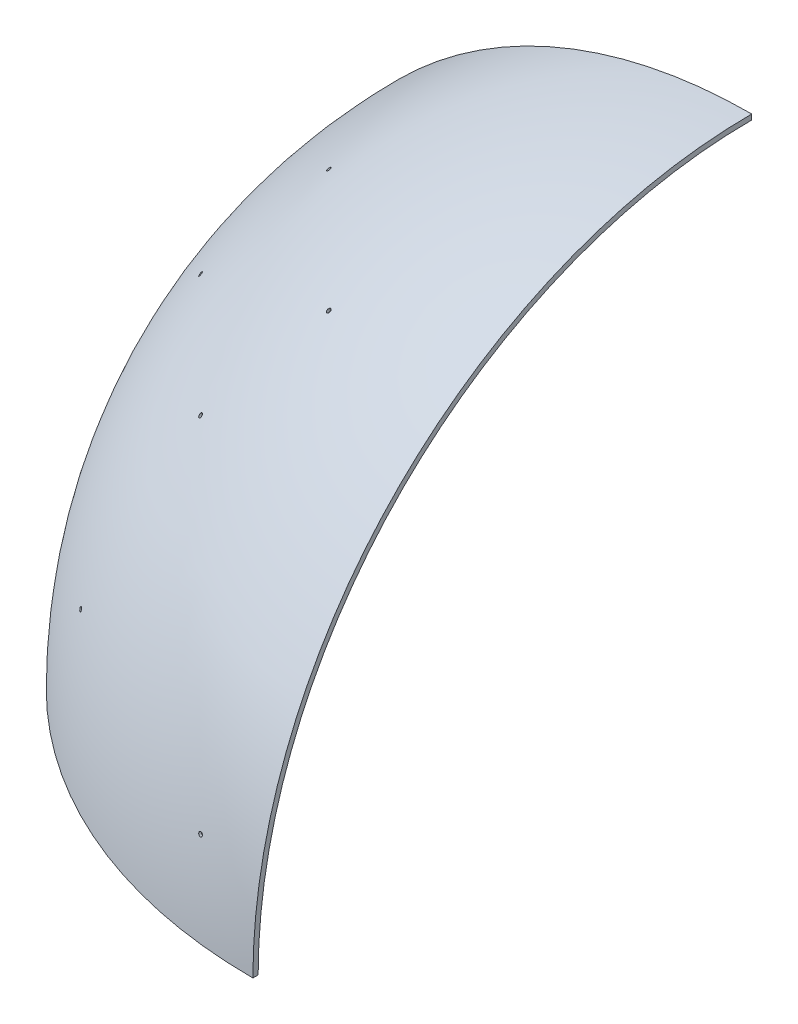
SolidWorks part; units mm, degrees
ref_plane "Front" through (0, 0, 0) normal (0, 0, 1) x (1, 0, 0)
ref_plane "Top" through (0, 0, 0) normal (0, 1, 0) x (1, 0, 0)
ref_plane "Right" through (0, 0, 0) normal (1, 0, 0) x (0, 0, -1)
sketch "Sketch1" plane through (0, 0, 0) normal (0, 0, 1) x (1, 0, 0)
  line L0 (0, 0) -> (-322.049, 0)
  line L1 (0, 0) -> (0, 286.8634)
  circle A0 centre (0, 0) radius 237.5
  circle A1 centre (0, 0) radius 235
  circle A2 centre (0, 0) radius 236.25
  dimension "D1" = 475
  dimension "D2" = 470
  dimension "D3" = 472.5
revolve "Revolve1" add sketch "Sketch1" angle 90 about L1 region at (-235.625, 3.3411, 0) region at (-236.875, 3.3588, 0)
sketch "Sketch2" plane through (0, 0, 0) normal (0, 0, 1) x (1, 0, 0)
  line L0 (0, 0) -> (0, 145.8567)
ref_plane "Plane1" through (0, 0, 0) normal (0.9914, 0, 0.1305) x (0, 1, 0)
sketch "Sketch3" plane through (0, 0, 0) normal (0.9914, 0, 0.1305) x (0, 1, 0)
  line L0 (0, 0) -> (49.8683, 282.8172)
  line L1 (0, 0) -> (0, 278.9678)
  line L2 (0.9848, -0.1736) -> (50.8531, 282.6436)
  line L3 (2.9544, -0.5209) -> (52.8227, 282.2963)
  circle A0 centre (0, 0) radius 236.25
  circle A1 centre (0, 0) radius 235
  circle A2 centre (0, 0) radius 237.5
  dimension "D3" = 472.5
  dimension "D4" = 470
  dimension "D5" = 475
  dimension "D1" = 10
  dimension "D2" = 1
  dimension "D6" = 3
revolve "Cut-Revolve1" cut sketch "Sketch3" angle 360 about L0 region at (-30.2766, 41.4081, 229.9734) region at (-30.4372, 41.6252, 231.1939) region at (-30.2415, 42.8839, 229.7068)
ref_plane "Plane2" through (0, 0, 0) normal (0.7071, 0, 0.7071) x (0, 1, 0)
sketch "Sketch4" plane through (0, 0, 0) normal (0, 1, 0) x (1, 0, 0)
  line L0 (0, 0) -> (-283.4977, 0)
  line L1 (0, 0) -> (-238.1017, -238.1017)
  dimension "D1" = 45
ref_plane "Plane3" through (0, 0, 0) normal (0, 0.7071, -0.7071) x (-1, 0, 0)
ref_axis "Axis1" through (34.9327, -34.9327, -34.9327) along (-0.5774, 0.5774, 0.5774)
ref_plane "Plane4" through (0, 0, 0) normal (-0.5, 0.7071, -0.5) x (-0.7071, 0, 0.7071)
mirror "Mirror2" about plane through (0, 0, 0) normal (-0.5, 0.7071, -0.5) of "Cut-Revolve1"
ref_axis "Axis3" through (0, -50, -70.7107) along (0, 0.5774, 0.8165)
pattern_circular "CirPattern3" count 2 every 120 about axis through (0, -50, -70.7107) along (0, 0.5774, 0.8165) of "Cut-Revolve1" reverse direction yes
mirror "Mirror5" about plane through (0, 0, 0) normal (0.7071, 0, 0.7071) of "Mirror2", "CirPattern3", "Cut-Revolve1"
ref_plane "Plane6" through (0, 0, 0) normal (0.8192, 0, 0.5736) x (0, 1, 0)
sketch "Sketch7" plane through (0, 0, 0) normal (0.8192, 0, 0.5736) x (0, 1, 0)
  line L0 (0, 0) -> (73.1392, 272.9592)
  line L1 (0, 0) -> (0, 268.8522)
  line L2 (2.8978, -0.7765) -> (76.037, 272.1828)
  line L3 (0.9659, -0.2588) -> (74.1051, 272.7004)
  circle A0 centre (0, 0) radius 237.5
  circle A1 centre (0, 0) radius 235
  circle A2 centre (0, 0) radius 236.25
  dimension "D4" = 475
  dimension "D5" = 470
  dimension "D6" = 472.5
  dimension "D1" = 15
  dimension "D2" = 3
  dimension "D3" = 1
revolve "Cut-Revolve2" cut sketch "Sketch7" angle 360 about L0 region at (-130.4692, 61.467, 186.3294) region at (-131.1618, 61.7905, 187.3184) region at (-130.2419, 62.9137, 186.0046)
mirror "Mirror6" about plane through (0, 0, 0) normal (0.7071, 0, 0.7071) of "Cut-Revolve2"
